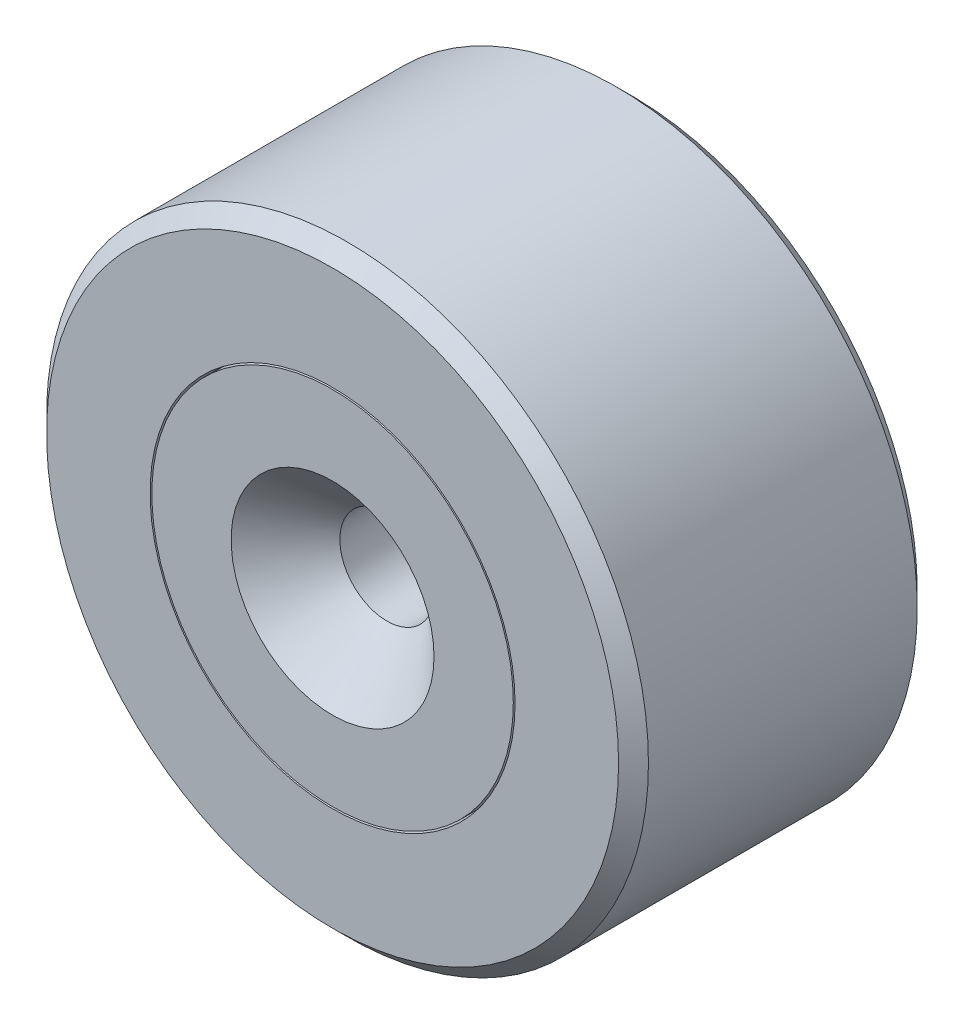
SolidWorks part; units mm, degrees
ref_plane "Front Plane" through (0, 0, 0) normal (0, 0, 1) x (1, 0, 0)
ref_plane "Top Plane" through (0, 0, 0) normal (0, 1, 0) x (1, 0, 0)
ref_plane "Right Plane" through (0, 0, 0) normal (1, 0, 0) x (0, 0, -1)
sketch "Sketch1" plane through (0, 0, 0) normal (1, 0, 0) x (0, 0, -1)
  line L0 (-3.935, 0) -> (3.935, 0) construction
  line L1 (0, 7.93) -> (0, -7.93) construction
  line L2 (3.5415, 7.93) -> (-3.5415, 7.93)
  line L3 (-3.5415, 7.93) -> (-3.935, 7.5365)
  line L4 (-3.935, 7.5365) -> (-3.935, 4.8086)
  line L5 (-3.935, 4.8086) -> (-1.953, 4.8086)
  line L6 (3.935, 4.8086) -> (1.953, 4.8086)
  line L7 (3.935, 7.5365) -> (3.935, 4.8086)
  line L8 (3.5415, 7.93) -> (3.935, 7.5365)
  line L9 (0, 7.93) -> (0, 4.4573) construction
  arc A0 (-1.953, 4.8086) -> (1.953, 4.8086) centre (0, 4.4573) cw
  circle A1 centre (0, 4.4573) radius 1.9844 construction
  point P14 (0, 4.7625)
  dimension "D3" = 3.9688
  dimension "D1" = 45
  dimension "Width" = 7.87
  dimension "OD" = 15.86
  dimension "D2" = 0.3935
  dimension "Shaft Dia" = 9.525
  dimension "D4" = 0.3512
  dimension "D5" = 3.4727
revolve "Revolve1" add sketch "Sketch1" angle 360 about L0
sketch "Sketch2" plane through (0, 0, 0) normal (1, 0, 0) x (0, 0, -1)
  line L0 (-3.935, 4.1061) -> (-1.953, 4.1061)
  line L1 (-3.935, 7.5365) -> (-3.935, -7.5365) construction
  line L2 (-3.935, 4.1061) -> (-3.935, 2.6735)
  line L3 (-3.935, 2.6735) -> (-2.5024, 1.241)
  line L4 (-2.5024, 1.241) -> (0.2016, 1.241)
  line L5 (0, 7.93) -> (0, -7.93) construction
  line L6 (0.2016, 1.241) -> (0, 2.473)
  line L7 (0, 2.473) -> (0, 4.7625) construction
  line L8 (-3.935, 4.1061) -> (-3.935, 1.241) construction
  line L9 (-3.935, 1.241) -> (-2.5024, 1.241) construction
  arc A0 (-1.953, 4.1061) -> (0, 2.473) centre (0, 4.4573) ccw
  arc A1 (1.953, 4.8086) -> (-1.953, 4.8086) centre (0, 4.4573) ccw construction
  circle A2 centre (0, 4.4573) radius 1.9844 construction
  dimension "D1" = 0.2016
  dimension "D2" = 2.5024
revolve "Revolve2" add sketch "Sketch2" angle 360 about L0
sketch "Sketch3" plane through (0, 0, 0) normal (1, 0, 0) x (0, 0, -1)
  line L0 (-3.935, 2.6735) -> (-2.5024, 1.241)
  line L1 (-2.5024, 1.241) -> (0, 1.241)
  line L2 (0, 1.241) -> (0, 2.473)
  line L3 (-3.935, 2.6735) -> (-3.935, 4.7625)
  line L6 (-3.935, 4.7625) -> (2.6724, 4.7625)
  line L7 (2.6724, 4.1061) -> (2.6724, 4.7625)
  line L11 (2.6724, 4.1061) -> (1.953, 4.1061)
  circle A0 centre (0, 4.4573) radius 1.9844 construction
  arc A1 (1.953, 4.1061) -> (0, 2.473) centre (0, 4.4573) cw
  dimension "D1" = 2.6724
revolve "Revolve3" add sketch "Sketch3" angle 360 about L0
ref_axis "Axis1" through (0, 0, -3.935) along (0, 0, 1)
equation "\"D2@Sketch1\" = \"Width@Sketch1\"*.05"
equation "\"D4@Sketch1\" = (((\"OD@Sketch1\"-\"Width@Sketch1\")/2)/3.25)/3.5"
equation "\"D5@Sketch1\" = \"D3@Sketch1\" * 7 / 8"
